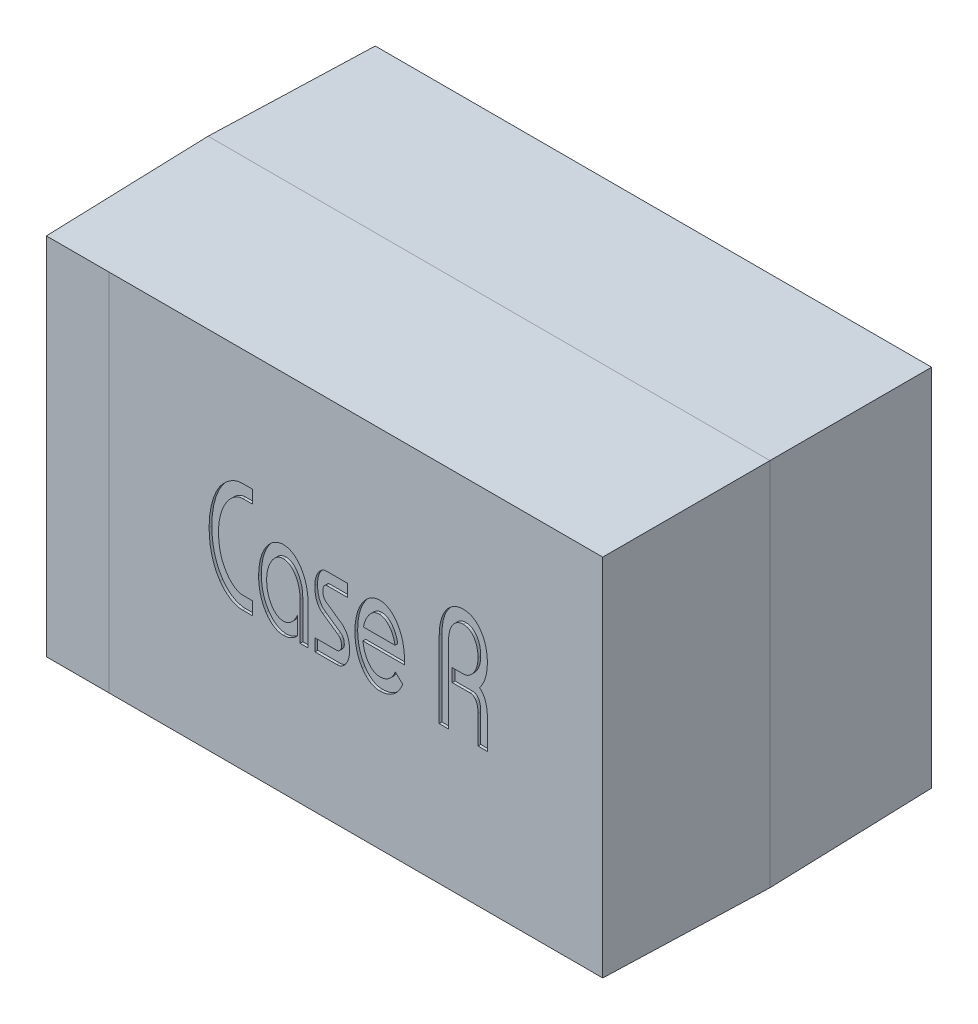
SolidWorks part; units mm, degrees
ref_plane "Front Plane" through (0, 0, 0) normal (0, 0, 1) x (1, 0, 0)
ref_plane "Top Plane" through (0, 0, 0) normal (0, 1, 0) x (1, 0, 0)
ref_plane "Right Plane" through (0, 0, 0) normal (1, 0, 0) x (0, 0, -1)
sketch "Sketch1" plane through (0, 0, 0) normal (0, 0, 1) x (1, 0, 0)
  line L1 (0, 0) -> (2.05, 0)
  line L2 (0, 0) -> (0, 1.35)
  line L3 (0, 1.35) -> (2.05, 1.35)
  line L4 (2.05, 0) -> (2.05, 1.35)
  dimension "D1" = 2.05
  dimension "D2" = 1.35
extrude "Boss-Extrude1" add sketch "Sketch1" along normal blind 1.2
chamfer "Chamfer3" distance 0.6 distance2 0.01 4 edges at (2.05, 0.675, 1.2) (1.025, 1.35, 1.2) (0, 0.675, 1.2) (1.025, 0, 1.2)
chamfer "Chamfer4" distance 0.01 distance2 0.6 4 edges at (1.025, 1.35, 0) (0, 0.675, 0) (1.025, 0, 0) (2.05, 0.675, 0)
sketch "Sketch3" plane through (0, 0, 1.2) normal (0, 0, 1) x (1, 0, 0)
  line L0 (2.04, 1.34) -> (0.01, 1.34) construction
  line L1 (0.2384, 1.34) -> (0.01, 1.34)
  line L2 (0.2384, 1.34) -> (0.2384, 0.01)
  line L3 (0.2384, 0.01) -> (0.01, 0.01)
  line L4 (0.01, 1.34) -> (0.01, 0.01)
  line L5 (0.01, 0.01) -> (2.04, 0.01) construction
extrude "Cut-Extrude1" cut sketch "Sketch3" against normal blind 0.01
sketch "Sketch4" plane through (0, 0, 1.19) normal (0, 0, 1) x (1, 0, 0)
  line L1 (0.01, 1.34) -> (0.2384, 1.34)
  line L2 (0.01, 1.34) -> (0.01, 0.01)
  line L3 (0.01, 0.01) -> (0.2384, 0.01)
  line L4 (0.2384, 1.34) -> (0.2384, 0.01)
  line L6 (0.01, 0.01) -> (0.2384, 0.01) construction
extrude "Boss-Extrude4" add sketch "Sketch4" along normal blind 0.01 separate body
sketch "Sketch5" plane through (0, 0, 1.2) normal (0, 0, 1) x (1, 0, 0)
  text T0 "Case R" font "Belgium" height 0.4
extrude "Cut-Extrude2" cut sketch "Sketch5" against normal blind 0.01
